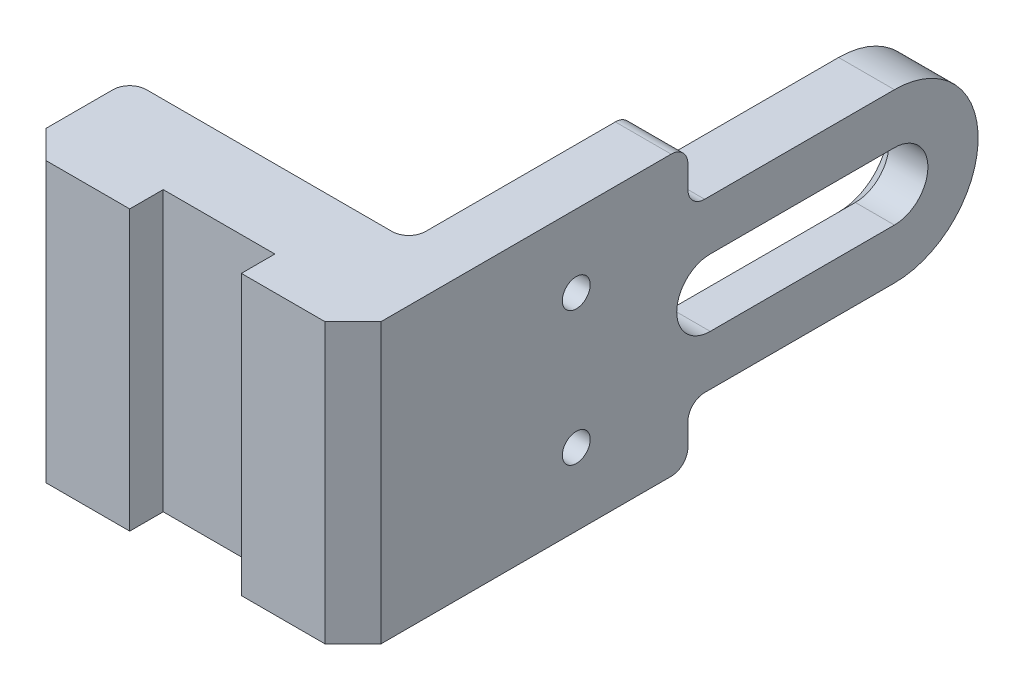
SolidWorks part; units mm, degrees
material "2014-T6"
ref_plane "Front Plane" through (0, 0, 0) normal (0, 0, 1) x (1, 0, 0)
ref_plane "Top Plane" through (0, 0, 0) normal (0, 1, 0) x (1, 0, 0)
ref_plane "Right Plane" through (0, 0, 0) normal (1, 0, 0) x (0, 0, -1)
sketch "Sketch1" plane through (0, 0, 0) normal (0, 1, 0) x (1, 0, 0)
  line L1 (0, 0) -> (-30, 0)
  line L2 (0, 0) -> (0, 10)
  line L3 (-5, 10) -> (-30, 10)
  line L4 (-30, 0) -> (-30, 10)
  line L5 (0, 0) -> (-5, 0)
  line L6 (0, 0) -> (0, 56)
  line L7 (0, 56) -> (-5, 56)
  line L8 (-5, 10) -> (-5, 56)
  dimension "D1" = 30
  dimension "D2" = 10
  dimension "D3" = 5
  dimension "D4" = 56
extrude "Boss-Extrude1" add sketch "Sketch1" along normal blind 25 contours L6 L7 L8 L3 L4 L1
sketch "Sketch2" plane through (0, 0, 0) normal (1, 0, 0) x (0, 0, -1)
  line L0 (0, 25) -> (56, 25) construction
  line L1 (30, 25) -> (56, 25)
  line L2 (30, 25) -> (30, 20)
  line L3 (30, 20) -> (56, 20)
  line L4 (56, 25) -> (56, 20)
  line L5 (56, 25) -> (56, 0) construction
  line L6 (0, 0) -> (56, 0) construction
  line L7 (30, 5) -> (56, 5)
  line L8 (30, 5) -> (30, 0)
  line L9 (30, 0) -> (56, 0)
  line L10 (56, 5) -> (56, 0)
  line L11 (0, 25) -> (0, 0) construction
  line L12 (0, 12.5) -> (97, 12.5) construction
  line L13 (56, 20) -> (56, 5)
  circle A0 centre (48.5, 12.5) radius 7.5
  dimension "D2" = 7.5
  dimension "D1" = 30
extrude "Cut-Extrude1" cut sketch "Sketch2" against normal blind 25 contours L4 L1 L2 L3 | A0 L13 L3 | A0 L7 L13 | L10 L7 L8 L9 region at (0, 22.5, -43) region at (0, 18.3247, -54.3247) region at (0, 6.6753, -54.3247) region at (0, 2.5, -43)
sketch "Sketch3" plane through (0, 0, 0) normal (1, 0, 0) x (0, 0, -1)
  line L0 (32, 12.5) -> (48.5, 12.5) construction
  line L1 (32, 15.5) -> (48.5, 15.5)
  line L2 (32, 9.5) -> (48.5, 9.5)
  line L3 (0, 12.5) -> (23.8442, 12.5) construction
  line L4 (0, 25) -> (0, 0) construction
  arc A0 (32, 15.5) -> (32, 9.5) centre (32, 12.5) ccw
  arc A1 (48.5, 9.5) -> (48.5, 15.5) centre (48.5, 12.5) ccw
  arc A2 (48.5, 5) -> (48.5, 20) centre (48.5, 12.5) ccw construction
  point P2 (40.25, 12.5)
  dimension "D1" = 3
  dimension "D2" = 32
  dimension "D3" = 48.5
extrude "Cut-Extrude2" cut sketch "Sketch3" against normal blind 25 contours L2 A1 L1 A0
fillet "Fillet1" radius 1.5 4 edges at (-2.5, 20, -30) (-2.5, 5, -30) (-2.5, 0, -30) (-2.5, 25, -30)
sketch "Sketch5" plane through (0, 0, 0) normal (1, 0, 0) x (0, 0, -1)
  line L0 (0, 0) -> (10, 0) construction
  line L1 (10, 25) -> (28.5, 25) construction
  circle A0 centre (20, 18.5) radius 3
  circle A1 centre (20, 6.5) radius 3
  circle A2 centre (20, 18.5) radius 1.25
  circle A3 centre (20, 6.5) radius 1.25
  point P11 (0, 0)
  dimension "D2" = 6
  dimension "D3" = 6
  dimension "D7" = 2.5
  dimension "D8" = 2.5
  dimension "D1" = 12
  dimension "D4" = 20
  dimension "D5" = 6.5
  dimension "D6" = 6.5
extrude "Cut-Extrude4" cut sketch "Sketch5" against normal blind 25 contours A2 | A3
extrude "Cut-Extrude5" cut sketch "Sketch5<4>" against normal blind 2.5 from offset 2.5 offset against normal yes
sketch "Sketch5<4>" plane through (0, 0, 0) normal (1, 0, 0) x (0, 0, -1) same geometry as "Sketch5"
sketch "Sketch7" plane through (0, 25, 0) normal (0, 1, 0) x (1, 0, 0)
  line L0 (0, 0) -> (-30, 0) construction
  line L1 (-20, 3) -> (-10, 3)
  line L2 (-20, 3) -> (-20, 0)
  line L3 (-20, 0) -> (-10, 0)
  line L4 (-10, 3) -> (-10, 0)
  line L5 (-30, 0) -> (-30, 10) construction
  dimension "D1" = 10
  dimension "D2" = 10
  dimension "D3" = 3
extrude "Cut-Extrude6" cut sketch "Sketch7" against normal through all contours L4 L3 L2 L1
chamfer "Chamfer1" distance 2.5 angle 45 2 edges at (0, 12.5, 0) (-30, 12.5, 0)
fillet "Fillet2" radius 1.5 2 edges at (-30, 12.5, -10) (-5, 12.5, -10)
chamfer "Chamfer2" distance 1.5 angle 45 4 edges at (-5, 9.5, -40.25) (-5, 12.5, -51.5) (-5, 12.5, -29) (-5, 15.5, -40.25)
